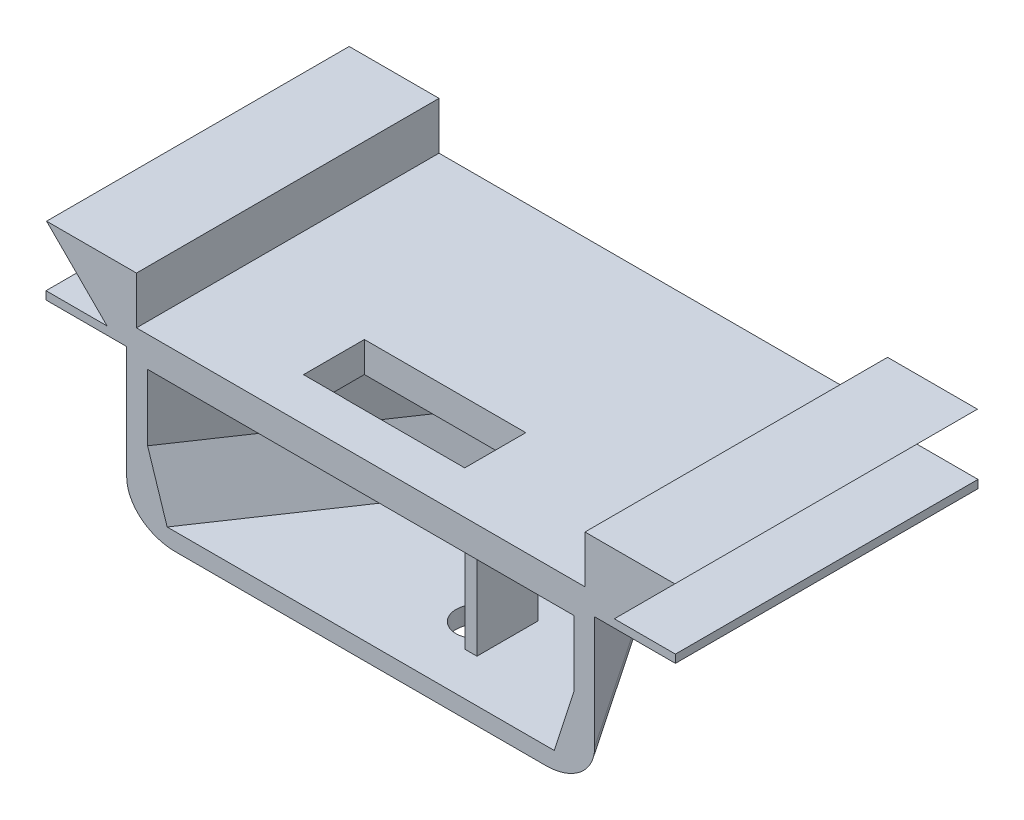
SolidWorks part; units mm, degrees
other "Camera1"
ref_plane "Front Plane" through (0, 0, 0) normal (0, 0, 1) x (1, 0, 0)
ref_plane "Top Plane" through (0, 0, 0) normal (0, 1, 0) x (1, 0, 0)
ref_plane "Right Plane" through (0, 0, 0) normal (1, 0, 0) x (0, 0, -1)
sketch "Sketch1" plane through (0, 0, 0) normal (0, 1, 0) x (1, 0, 0)
  line L0 (0, 0) -> (-116, 0)
  line L1 (-116, 0) -> (-75.5008, 60)
  line L2 (-75.5008, 60) -> (-40.5008, 60)
  line L3 (-40.5008, 60) -> (0, 0)
  dimension "D1" = 60
  dimension "D2" = 116
  dimension "D3" = 35
  dimension "D5" = 72.39
  dimension "D6" = 72.3891
extrude "Boss-Extrude1" add sketch "Sketch1" against normal blind 40
shell "Shell1" thickness 4.2918 removed face at (-58, -20, 0)
sketch "Sketch5" plane through (0, 0, -55.7082) normal (0, 0, 1) x (1, 0, 0)
  line L0 (-42.7818, -4.2918) -> (-73.2197, -4.2918) construction
  line L1 (-53.2497, -23.0418) -> (-61.7497, -23.0418)
  line L2 (-53.2497, -23.0418) -> (-53.2497, -14.5418)
  line L3 (-53.2497, -14.5418) -> (-61.7497, -14.5418)
  line L4 (-61.7497, -23.0418) -> (-61.7497, -14.5418)
  line L5 (-73.2197, -35.7082) -> (-73.2197, -4.2918) construction
  line L7 (-42.7818, -35.7082) -> (-42.7818, -4.2918) construction
  dimension "D1" = 11.47
  dimension "D2" = 8.5
  dimension "D3" = 10.25
  dimension "D4" = 10.4679
extrude "Cut-Extrude5" cut sketch "Sketch5" against normal blind 6
chamfer "Chamfer3" distance 15 angle 15 2 edges at (-92.0209, -35.7082, -27.8541) (-23.9799, -35.7082, -27.8541) first distance on face at (-92.0209, -20, -27.8541) first distance on face at (-23.9799, -20, -27.8541)
fillet "Fillet1" radius 10 2 edges at (-20.2504, -40, -30) (-95.7504, -40, -30)
fillet "Fillet2" radius 5 5 edges at (-40.5008, -15, -60) (-44.0345, -37.0711, -60) (-75.5008, -15, -60) (-71.9671, -37.0711, -60) (-58.0008, -40, -60)
sketch "Sketch12" plane through (0, -40, 0) normal (0, -1, 0) x (-1, 0, 0)
  circle A0 centre (47.2824, 18.1003) radius 5.2
sketch "Sketch13" plane through (0, -4.2918, 0) normal (0, -1, 0) x (1, 0, 0)
  line L1 (-39.8423, -25.7584) -> (-42.8423, -25.7584)
  line L2 (-39.8423, -25.7584) -> (-39.8423, -10.6584)
  line L3 (-39.8423, -10.6584) -> (-42.8423, -10.6584)
  line L4 (-42.8423, -25.7584) -> (-42.8423, -10.6584)
  dimension "D1" = 3
extrude "Boss-Extrude3" add sketch "Sketch13" along normal blind 35
extrude "Cut-Extrude12" cut sketch "Sketch12" against normal blind 9
sketch "Sketch15" plane through (0, 0, 0) normal (0, 1, 0) x (1, 0, 0)
  line L8 (-136, 75) -> (20, 75)
  line L9 (20, 0) -> (20, 75)
  line L10 (20, 0) -> (-136, 0)
  line L11 (-136, 0) -> (-136, 75)
extrude "Boss-Extrude7" add sketch "Sketch15" along normal blind 15
sketch "Sketch16" plane through (0, 0, 0) normal (0, 0, 1) x (1, 0, 0)
  line L1 (20.1, 15.2414) -> (20.1, -0.1)
  line L3 (20.1, -0.1) -> (4.7586, -0.1)
  line L6 (4.7586, -0.1) -> (20.1, 15.2414)
  line L8 (20, 15) -> (20, 0) construction
  line L9 (20, 0) -> (5, 0) construction
  line L10 (0, 0) -> (20, 0) construction
  line L11 (5, 0) -> (20, 15) construction
  dimension "D1" = 15
  dimension "D2" = 0.1
extrude "Cut-Extrude14" cut sketch "Sketch16" against normal blind 75
sketch "Sketch17" plane through (0, 0, 0) normal (0, 0, 1) x (1, 0, 0)
  line L0 (-136, 15) -> (-136, 0) construction
  line L1 (-136, 0) -> (-121, 0) construction
  line L2 (-136, 0) -> (-116, 0) construction
  line L3 (-121, 0) -> (-136, 15) construction
  line L4 (-120.7586, -0.1) -> (-136.1, 15.2414)
  line L5 (-136.1, 15.2414) -> (-136.1, -0.1)
  line L6 (-136.1, -0.1) -> (-120.7586, -0.1)
  dimension "D1" = 0.1
extrude "Cut-Extrude15" cut sketch "Sketch17" against normal blind 75
sketch "Sketch18" plane through (0, 0, 0) normal (0, -1, 0) x (1, 0, 0)
  line L0 (-116, 0) -> (-121, 0)
  line L1 (-121, 0) -> (-136.0045, 0)
  line L2 (-136.0045, 0) -> (-136.0045, -75)
  line L3 (-136.0045, -75) -> (-121, -75)
  line L5 (20.0045, -75) -> (20.0045, 0)
  line L6 (20.0045, 0) -> (-116, 0)
  line L7 (20.0045, -75) -> (4.5, -75)
  line L8 (-121, -75) -> (4.5, -75)
  dimension "D1" = 75
extrude "Boss-Extrude8" add sketch "Sketch18" along normal blind 2 contours L8 L7 L5 L6 L0 L1 L2 L3
sketch "Sketch20" plane through (0, -2, 0) normal (0, -1, 0) x (-1, 0, 0)
  line L1 (42.8423, 25.7218) -> (72.8207, 25.7218)
  line L2 (42.8423, 25.7218) -> (42.8423, 10.6218)
  line L3 (42.8423, 10.6218) -> (72.8207, 10.6218)
  line L4 (72.8207, 25.7218) -> (72.8207, 10.6218)
extrude "Cut-Extrude17" cut sketch "Sketch20" against normal blind 39 contours L2 L1 L4 L3
sketch "Sketch21" plane through (0, 0, 0) normal (0, 0, 1) x (1, 0, 0)
  line L6 (-135.8586, 15) -> (19.8586, 15) construction
  line L7 (-2.413, 15) -> (-113.583, 15)
  line L9 (-2.413, 15) -> (-113.583, 15)
  line L11 (-2.413, 15) -> (-2.413, 3.2309)
  line L12 (-2.413, 3.2309) -> (-113.583, 3.2309)
  line L13 (-113.583, 15) -> (-113.583, 3.2309)
extrude "Cut-Extrude18" cut sketch "Sketch21" against normal blind 80 contours L11 L9 L13 L12
sketch "Sketch22" plane through (-42.8423, 0, 0) normal (-1, 0, 0) x (0, 0, 1)
  line L1 (-10.6584, -35.7082) -> (-18.2084, -35.7082)
  line L2 (-10.6584, -35.7082) -> (-10.6584, -10.7935)
  line L3 (-10.6584, -10.7935) -> (-18.2084, -10.7935)
  line L4 (-18.2084, -35.7082) -> (-18.2084, -10.7935)
  circle A0 centre (-18.2084, -10.7935) radius 2.4
  dimension "D1" = 4.8
extrude "Cut-Extrude19" cut sketch "Sketch22" against normal blind 10 contours A0
sketch "Sketch23" plane through (0, 0, -55.7082) normal (0, 0, 1) x (1, 0, 0)
  line L0 (-61.7497, -23.0418) -> (-70.3928, -23.0418)
  line L1 (-70.3928, -23.0418) -> (-70.3928, -19.08)
  line L2 (-70.3928, -19.08) -> (-68.2428, -19.08)
  circle A0 centre (-68.2428, -19.08) radius 1.12
extrude "Cut-Extrude20" cut sketch "Sketch23" against normal blind 10 contours A0
sketch "Sketch24" plane through (0, 0, -55.7082) normal (0, 0, 1) x (1, 0, 0)
  line L0 (-53.2497, -23.0418) -> (-45.0928, -23.0418)
  line L1 (-45.0928, -23.0418) -> (-45.0928, -19.08)
  line L2 (-45.0928, -19.08) -> (-47.2428, -19.08)
  circle A0 centre (-47.2428, -19.08) radius 1.12
extrude "Cut-Extrude21" cut sketch "Sketch24" against normal blind 10 contours A0
sketch "Sketch25" plane through (0, 0, -55.7082) normal (0, 0, 1) x (1, 0, 0)
  line L0 (-68.2428, -17.96) -> (-68.2428, -6.61)
  circle A0 centre (-68.2428, -19.08) radius 1.12 construction
  circle A1 centre (-68.2428, -6.61) radius 1.12
extrude "Cut-Extrude22" cut sketch "Sketch25" against normal blind 10 contours A1
sketch "Sketch26" plane through (0, 0, -55.7082) normal (0, 0, 1) x (1, 0, 0)
  line L0 (-47.2428, -17.96) -> (-47.2428, -6.61)
  circle A0 centre (-47.2428, -19.08) radius 1.12 construction
  circle A1 centre (-47.2428, -6.61) radius 1.12
extrude "Cut-Extrude23" cut sketch "Sketch26" against normal blind 10 contours A1
sketch "Sketch27" plane through (0, -4.2918, 0) normal (0, -1, 0) x (-1, 0, 0)
  line L1 (42.8423, 10.6584) -> (82.8423, 10.6584)
  line L2 (42.8423, 10.6584) -> (42.8423, 25.7584)
  line L3 (42.8423, 25.7584) -> (82.8423, 25.7584)
  line L4 (82.8423, 10.6584) -> (82.8423, 25.7584)
extrude "Cut-Extrude24" cut sketch "Sketch27" against normal blind 19 contours L2 L1 L4 L3
